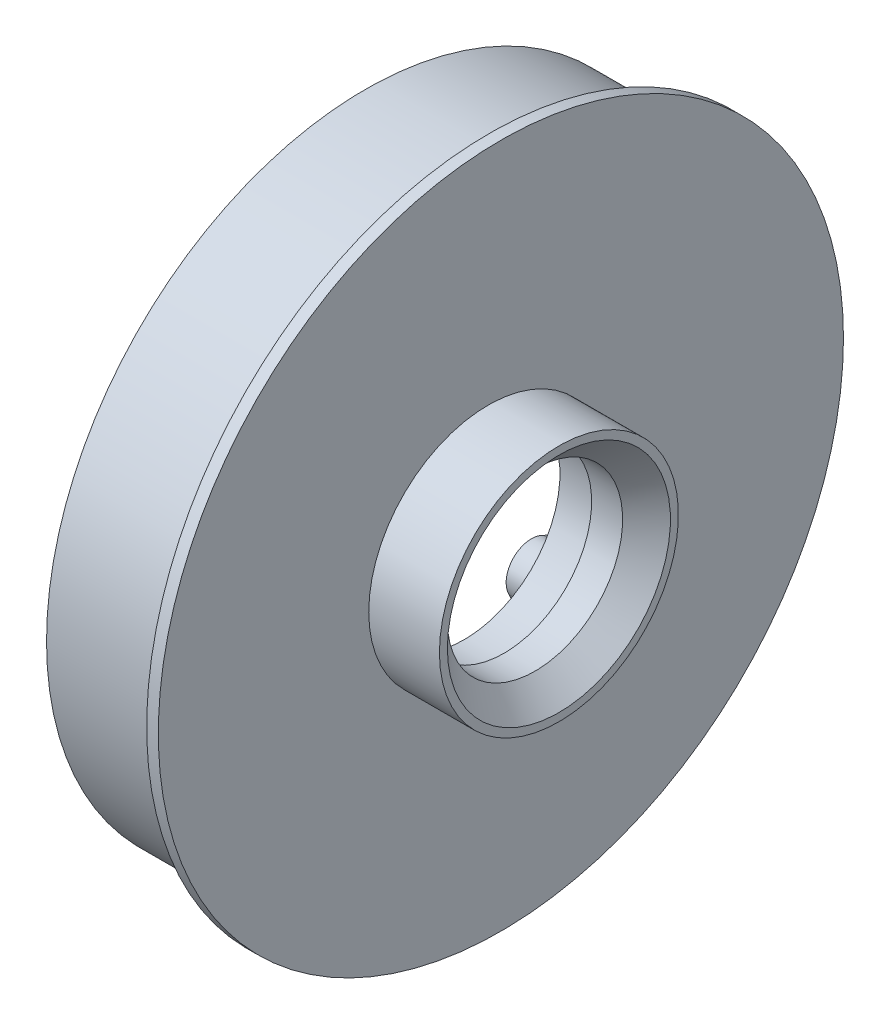
SolidWorks part; units mm, degrees
ref_plane "Front Plane" through (0, 0, 0) normal (0, 0, 1) x (1, 0, 0)
ref_plane "Top Plane" through (0, 0, 0) normal (0, 1, 0) x (1, 0, 0)
ref_plane "Right Plane" through (0, 0, 0) normal (1, 0, 0) x (0, 0, -1)
sketch "Sketch2" plane through (0, 0, 0) normal (0, 0, 1) x (1, 0, 0)
  line L0 (0, 0) -> (58.591, 0) construction
  line L2 (0, 0) -> (18.4, 0)
  line L3 (0, 0) -> (0, 2.5)
  line L4 (0, 2.5) -> (18.4, 2.5)
  line L5 (18.4, 0) -> (18.4, 2.5)
  line L6 (6.0094, 2.5) -> (6.0094, 6)
  line L11 (6.0094, 6) -> (9.9794, 6)
  line L16 (12.9794, 6) -> (12.9794, 3)
  line L17 (12.9794, 3) -> (13.6398, 3)
  line L18 (13.6398, 3) -> (13.6398, 2.5)
  line L19 (13.6398, 2.5) -> (6.0094, 2.5)
  line L22 (13.6398, 2.5) -> (16.1198, 2.5)
  line L23 (13.6398, 2.5) -> (13.6398, 4)
  line L24 (13.6398, 4) -> (16.1198, 4)
  line L25 (16.1198, 2.5) -> (16.1198, 4)
  line L27 (6.0094, 6) -> (9.9794, 6)
  line L28 (6.0094, 6) -> (6.0094, 9)
  line L29 (6.0094, 9) -> (9.9794, 9)
  line L30 (9.9794, 6) -> (9.9794, 9)
  line L31 (6.0094, 9) -> (6.0094, 8.25)
  line L32 (6.0094, 8.25) -> (5.0094, 8.25)
  line L33 (8.6609, 22.001) -> (8.6609, 12.476) construction
  line L34 (5.0094, 12.476) -> (12.3124, 12.476)
  line L35 (9.9794, 9) -> (12.3124, 9)
  line L36 (5.0094, 7.9375) -> (1.8344, 7.9375)
  line L37 (5.0094, 8.25) -> (5.0094, 12.476)
  line L38 (5.0094, 7.9375) -> (5.0094, 13.9365)
  line L39 (5.0094, 13.9365) -> (1.8344, 13.9365)
  line L40 (1.8344, 7.9375) -> (1.8344, 13.9365)
  line L41 (5.0094, 22.001) -> (12.3124, 22.001)
  line L42 (5.0094, 22.001) -> (5.0094, 30.1625)
  line L43 (5.0094, 30.1625) -> (12.3124, 30.1625)
  line L44 (12.3124, 22.001) -> (12.3124, 30.1625)
  line L49 (16.6398, 22.001) -> (16.6398, 7.5)
  line L51 (23.0198, 7.5) -> (23.0198, 6.5)
  line L54 (16.1198, 4) -> (13.6398, 4)
  line L56 (18.0398, 7.5) -> (23.0198, 7.5)
  line L57 (13.3124, 22.001) -> (16.6398, 22.001)
  line L58 (16.1198, 3.5) -> (20.0198, 3.5)
  line L59 (29.9098, 14) -> (26.9098, 11)
  line L60 (4.0094, 31.75) -> (18.0398, 31.75)
  line L61 (18.0398, 7.5) -> (23.0198, 7.5)
  line L62 (18.0398, 7.5) -> (18.0398, 12)
  line L63 (18.0398, 12) -> (23.0198, 12)
  line L64 (23.0198, 7.5) -> (23.0198, 12)
  line L65 (18.0398, 31.75) -> (18.0398, 12)
  line L66 (23.0198, 11) -> (26.9098, 11)
  line L67 (34.8098, 23) -> (31.3098, 19.5)
  line L68 (35.8098, 31) -> (38.7998, 33.99)
  line L69 (29.9098, 14) -> (29.9098, 15)
  line L70 (29.9098, 15) -> (22.9398, 15)
  line L71 (22.9398, 15) -> (21.0398, 15)
  line L72 (18.0398, 7.5) -> (16.6398, 7.5)
  line L73 (21.0398, 15) -> (21.0398, 43)
  line L74 (19.5798, 40) -> (9.6198, 40)
  line L75 (9.6198, 40) -> (4.0094, 40)
  line L76 (21.0398, 43) -> (19.5798, 43)
  line L77 (22.9398, 15) -> (29.9098, 15)
  line L78 (22.9398, 15) -> (22.9398, 21)
  line L79 (22.9398, 21) -> (29.9098, 21)
  line L80 (29.9098, 15) -> (29.9098, 21)
  line L81 (9.6198, 40) -> (19.5798, 40)
  line L82 (9.6198, 40) -> (9.6198, 50)
  line L83 (9.6198, 50) -> (19.5798, 50)
  line L84 (19.5798, 40) -> (19.5798, 50)
  line L85 (4.0094, 40) -> (4.0094, 31.75)
  line L86 (12.9794, 3) -> (12.9794, 2.5)
  line L87 (31.3098, 19.5) -> (29.9098, 19.5)
  line L88 (21.4694, 63.5) -> (21.4694, 51.308)
  line L89 (21.4694, 63.5) -> (25.9398, 63.5)
  line L90 (25.9398, 63.5) -> (25.9398, 25)
  line L91 (27.8398, 25) -> (25.9398, 25)
  line L92 (9.6198, 48) -> (8.1598, 48)
  line L93 (8.1598, 48) -> (8.1598, 53.476)
  line L94 (8.1598, 53.476) -> (19.5798, 53.476)
  line L95 (19.5798, 53.476) -> (19.5798, 50)
  line L96 (13.8698, 63.001) -> (13.8698, 53.476) construction
  line L97 (8.1598, 63.001) -> (19.5798, 63.001)
  line L98 (8.1598, 63.001) -> (8.1598, 68.2625)
  line L99 (8.1598, 68.2625) -> (19.5798, 68.2625)
  line L100 (19.5798, 63.001) -> (19.5798, 68.2625)
  line L101 (12.9794, 6) -> (11.9794, 6)
  line L102 (8.1598, 44.825) -> (4.9848, 44.825)
  line L103 (8.1598, 44.825) -> (8.1598, 54.9365)
  line L104 (8.1598, 54.9365) -> (4.9848, 54.9365)
  line L106 (9.9794, 6) -> (10.8794, 6)
  line L107 (27.8398, 25) -> (34.8098, 25)
  line L108 (34.8098, 25) -> (34.8098, 23)
  line L109 (0, 0) -> (-2, 0)
  line L110 (0, 0) -> (0, 11)
  line L111 (27.8398, 25) -> (34.8098, 25)
  line L112 (27.8398, 25) -> (27.8398, 32.5)
  line L113 (27.8398, 32.5) -> (34.8098, 32.5)
  line L114 (34.8098, 25) -> (34.8098, 32.5)
  line L115 (35.8098, 31) -> (34.8098, 31)
  line L116 (27.8398, 32.5) -> (27.8398, 64.5)
  line L117 (20.5373, 74.025) -> (6.2023, 74.025)
  line L118 (6.2023, 74.025) -> (6.2023, 76.2)
  line L119 (38.7998, 47.29) -> (30.8398, 55.25)
  line L120 (0, 11) -> (-2, 11)
  line L121 (38.7998, 43.815) -> (30.8623, 43.815)
  line L123 (-4.8152, 69.85) -> (1.5348, 76.2)
  line L124 (38.7998, 47.29) -> (38.7998, 33.99)
  line L125 (-2, 0) -> (-2, 11)
  line L126 (38.7998, 37.465) -> (30.8623, 37.465)
  line L127 (30.8623, 43.815) -> (30.8623, 37.465)
  line L128 (6.0094, 2.5) -> (6.0094, 0)
  line L129 (-0.0152, 63.5) -> (-0.0152, 30)
  line L132 (4.9848, 63.5) -> (-0.0152, 63.5)
  line L136 (-1.8152, 30) -> (-11.7752, 30)
  line L138 (-13.7752, 25.4) -> (-2, 25.4)
  line L139 (-2, 25.4) -> (-2, 11.5)
  line L140 (27.8398, 64.5) -> (20.5373, 64.5)
  line L141 (-1.8152, 30) -> (-11.7752, 30)
  line L142 (-1.8152, 30) -> (-1.8152, 39)
  line L143 (-1.8152, 39) -> (-11.7752, 39)
  line L144 (-11.7752, 30) -> (-11.7752, 39)
  line L145 (20.5373, 64.5) -> (20.5373, 74.025)
  line L146 (-12.7752, 37) -> (-12.7752, 47.29)
  line L147 (-12.7752, 37) -> (-11.7752, 37)
  line L148 (30.8398, 55.25) -> (30.8398, 76.2)
  line L149 (11.9794, 6) -> (11.9794, 5.45)
  line L154 (-2, 11.5) -> (0.5, 11.5)
  line L155 (4.9848, 60.6197) -> (24.0348, 60.6197)
  line L160 (4.9848, 60.6197) -> (4.9848, 55.8572)
  line L161 (4.9848, 55.8572) -> (24.0348, 55.8572)
  line L166 (24.0348, 60.6197) -> (24.0348, 55.8572)
  line L167 (4.9848, 60.6197) -> (24.0348, 55.8572) construction
  line L172 (4.9848, 55.8572) -> (24.0348, 60.6197) construction
  line L173 (24.0348, 62.2072) -> (25.9398, 62.2072)
  line L174 (11.9794, 5.45) -> (10.8794, 5.45)
  line L175 (10.8794, 6) -> (10.8794, 5.45)
  line L176 (24.0348, 62.2072) -> (24.0348, 54.2697)
  line L177 (24.0348, 54.2697) -> (25.9398, 54.2697)
  line L178 (25.9398, 62.2072) -> (25.9398, 54.2697)
  line L179 (24.0348, 62.2072) -> (25.9398, 54.2697) construction
  line L180 (24.0348, 54.2697) -> (25.9398, 62.2072) construction
  line L181 (3, 19.6197) -> (15.7, 19.6197)
  line L182 (3, 19.6197) -> (3, 14.8572)
  line L183 (3, 14.8572) -> (15.7, 14.8572)
  line L184 (15.7, 19.6197) -> (15.7, 14.8572)
  line L185 (3, 19.6197) -> (15.7, 14.8572) construction
  line L186 (3, 14.8572) -> (15.7, 19.6197) construction
  line L187 (15.7, 21.2072) -> (16.6398, 21.2072)
  line L188 (15.7, 21.2072) -> (15.7, 13.2697)
  line L189 (15.7, 13.2697) -> (16.6398, 13.2697)
  line L190 (16.6398, 21.2072) -> (16.6398, 13.2697)
  line L191 (15.7, 21.2072) -> (16.6398, 13.2697) construction
  line L192 (15.7, 13.2697) -> (16.6398, 21.2072) construction
  line L193 (0.5, 11.5) -> (0.5, 6.9375)
  line L194 (0.5, 6.9375) -> (1.8344, 6.9375)
  line L195 (23.0198, 6.5) -> (20.0198, 3.5)
  line L196 (4.9848, 63.5) -> (4.9848, 54.9365)
  line L197 (3, 43.825) -> (4.9848, 43.825)
  line L198 (1.8344, 6.9375) -> (1.8344, 7.9375)
  line L199 (6.0094, 0) -> (12.9794, 0)
  line L200 (12.9794, 0) -> (12.9794, 2.5)
  line L201 (18.0398, 31.75) -> (18.0398, 35.875)
  line L202 (18.0398, 35.875) -> (21.0398, 35.875)
  line L203 (30.8398, 76.2) -> (6.2023, 76.2)
  line L204 (2.7573, 69.85) -> (7.2023, 69.85) construction
  line L205 (7.2023, 67.4688) -> (26.2523, 67.4688)
  line L206 (7.2023, 74.025) -> (7.2023, 64.5)
  line L207 (7.2023, 64.5) -> (-1.8152, 64.5)
  line L208 (-1.8152, 64.5) -> (-1.8152, 39)
  line L209 (-12.7752, 47.29) -> (-4.8152, 55.25)
  line L210 (-4.8152, 55.25) -> (-4.8152, 69.85)
  line L211 (7.2023, 67.4688) -> (7.2023, 72.2312)
  line L212 (7.2023, 72.2312) -> (26.2523, 72.2313)
  line L213 (26.2523, 67.4688) -> (26.2523, 72.2313)
  line L214 (26.2523, 73.8187) -> (30.8398, 73.8187)
  line L215 (26.2523, 73.8187) -> (26.2523, 65.8813)
  line L216 (26.2523, 65.8813) -> (30.8398, 65.8813)
  line L217 (30.8398, 73.8187) -> (30.8398, 65.8813)
  line L218 (2.7573, 72.2313) -> (24.9823, 72.2313)
  line L219 (2.7573, 72.2313) -> (2.7573, 67.4687)
  line L220 (2.7573, 67.4687) -> (24.9823, 67.4687)
  line L221 (24.9823, 72.2313) -> (24.9823, 67.4687)
  line L222 (24.9823, 69.85) -> (20.5373, 69.85) construction
  line L223 (21.4694, 51.308) -> (22.9398, 51.308)
  line L224 (22.9398, 51.308) -> (22.9398, 21)
  line L225 (13.6398, 4) -> (13.6398, 12.2697)
  line L226 (13.6398, 12.2697) -> (13.3124, 12.2697)
  line L227 (13.3124, 12.2697) -> (13.3124, 22.001)
  line L228 (12.3124, 9) -> (12.3124, 12.476)
  line L229 (-1.8152, 30) -> (-0.0152, 30)
  line L230 (8.1598, 65.6317) -> (2.7573, 65.6317) construction
  line L231 (19.5798, 65.6317) -> (24.9823, 65.6317) construction
  line L232 (1.5348, 76.2) -> (6.2023, 76.2)
  line L233 (-11.7752, 30) -> (-13.7752, 30)
  line L234 (-13.7752, 30) -> (-13.7752, 25.4)
  line L235 (3, 13.9365) -> (3, 43.825)
  line L236 (4.9848, 54.9365) -> (4.9848, 44.825)
  line L237 (4.9848, 43.825) -> (4.9848, 44.825)
  circle A0 centre (26.8898, 25.95) radius 0.95
  circle A1 centre (21.9898, 15.95) radius 0.95
  circle A2 centre (17.3398, 8.2) radius 0.7
  circle A3 centre (10.4294, 6.45) radius 0.45
  circle A4 centre (-0.9152, 30.9) radius 0.9
  point P7 (24.9873, 58.2385)
  point P131 (16.1699, 17.2385)
  point P135 (14.5098, 58.2385)
  point P146 (9.35, 17.2385)
sketch "Sketch3" plane through (0, 0, 0) normal (1, 0, 0) x (0, 0, -1)
  line L0 (0, 0) -> (0, 69.85) construction
  line L1 (0, 0) -> (13.6271, 68.5079) construction
  line L2 (0, 0) -> (0, 58.2385) construction
  line L3 (0, 0) -> (50.436, 29.1192) construction
  line L4 (0, 0) -> (0, 31.75) construction
  line L5 (0, 0) -> (12.1502, 29.3332) construction
  line L6 (0, 0) -> (0, 17.2385) construction
  line L7 (0, 0) -> (14.929, 8.6192) construction
  line L8 (0, 0) -> (0, 58.2385) construction
  line L9 (0, 0) -> (50.436, 29.1192) construction
  line L10 (0, 0) -> (5.9583, 29.9542) construction
  line L11 (0, 0) -> (16.9677, 25.394) construction
  circle A0 centre (0, 0) radius 69.85 construction
  circle A1 centre (0, 0) radius 58.2385 construction
  circle A2 centre (0, 0) radius 31.75 construction
  circle A3 centre (0, 0) radius 17.2385 construction
  circle A4 centre (0, 69.85) radius 3.175
  circle A5 centre (0, 58.2385) radius 4.7625
  circle A6 centre (0, 31.75) radius 3.175
  circle A7 centre (0, 17.2385) radius 4.7625
  circle A8 centre (13.6271, 68.5079) radius 3.175
  circle A9 centre (26.7304, 64.533) radius 3.175
  circle A10 centre (38.8066, 58.0782) radius 3.175
  circle A11 centre (49.3914, 49.3914) radius 3.175
  circle A12 centre (58.0782, 38.8066) radius 3.175
  circle A13 centre (64.533, 26.7304) radius 3.175
  circle A14 centre (68.5079, 13.6271) radius 3.175
  circle A15 centre (69.85, 0) radius 3.175
  circle A16 centre (68.5079, -13.6271) radius 3.175
  circle A17 centre (64.533, -26.7304) radius 3.175
  circle A18 centre (58.0782, -38.8066) radius 3.175
  circle A19 centre (49.3914, -49.3914) radius 3.175
  circle A20 centre (38.8066, -58.0782) radius 3.175
  circle A21 centre (26.7304, -64.533) radius 3.175
  circle A22 centre (13.6271, -68.5079) radius 3.175
  circle A23 centre (0, -69.85) radius 3.175
  circle A24 centre (-13.6271, -68.5079) radius 3.175
  circle A25 centre (-26.7304, -64.533) radius 3.175
  circle A26 centre (-38.8066, -58.0782) radius 3.175
  circle A27 centre (-49.3914, -49.3914) radius 3.175
  circle A28 centre (-58.0782, -38.8066) radius 3.175
  circle A29 centre (-64.533, -26.7304) radius 3.175
  circle A30 centre (-68.5079, -13.6271) radius 3.175
  circle A31 centre (-69.85, 0) radius 3.175
  circle A32 centre (-68.5079, 13.6271) radius 3.175
  circle A33 centre (-64.533, 26.7304) radius 3.175
  circle A34 centre (-58.0782, 38.8066) radius 3.175
  circle A35 centre (-49.3914, 49.3914) radius 3.175
  circle A36 centre (-38.8066, 58.0782) radius 3.175
  circle A37 centre (-26.7304, 64.533) radius 3.175
  circle A38 centre (-13.6271, 68.5079) radius 3.175
  circle A47 centre (50.436, 29.1192) radius 4.7625
  circle A48 centre (50.436, -29.1192) radius 4.7625
  circle A49 centre (0, -58.2385) radius 4.7625
  circle A50 centre (-50.436, -29.1192) radius 4.7625
  circle A51 centre (-50.436, 29.1192) radius 4.7625
  circle A58 centre (12.1502, 29.3332) radius 3.175
  circle A59 centre (22.4506, 22.4506) radius 3.175
  circle A60 centre (29.3332, 12.1502) radius 3.175
  circle A61 centre (31.75, 0) radius 3.175
  circle A62 centre (29.3332, -12.1502) radius 3.175
  circle A63 centre (22.4506, -22.4506) radius 3.175
  circle A64 centre (12.1502, -29.3332) radius 3.175
  circle A65 centre (0, -31.75) radius 3.175
  circle A66 centre (-12.1502, -29.3332) radius 3.175
  circle A67 centre (-22.4506, -22.4506) radius 3.175
  circle A68 centre (-29.3332, -12.1502) radius 3.175
  circle A69 centre (-31.75, 0) radius 3.175
  circle A70 centre (-29.3332, 12.1502) radius 3.175
  circle A71 centre (-22.4506, 22.4506) radius 3.175
  circle A72 centre (14.929, 8.6192) radius 4.7625
  circle A73 centre (14.929, -8.6192) radius 4.7625
  circle A74 centre (0, -17.2385) radius 4.7625
  circle A75 centre (-14.929, -8.6192) radius 4.7625
  circle A76 centre (-14.929, 8.6192) radius 4.7625
  circle A77 centre (0, 0) radius 50
  circle A78 centre (0, 0) radius 9
  circle A79 centre (-12.1502, 29.3332) radius 3.175
  circle A80 centre (0, 0) radius 76.2
  circle A81 centre (0, 0) radius 74.025
  circle A82 centre (0, 69.85) radius 3.9687
  circle A83 centre (49.3914, 49.3914) radius 3.9687
  circle A84 centre (69.85, 0) radius 3.9688
  circle A85 centre (49.3914, -49.3914) radius 3.9687
  circle A86 centre (0, -69.85) radius 3.9687
  circle A87 centre (-49.3914, -49.3914) radius 3.9687
  circle A88 centre (-69.85, 0) radius 3.9688
  circle A89 centre (-49.3914, 49.3914) radius 3.9687
  circle A90 centre (0, 69.85) radius 2.3812
  circle A91 centre (13.6271, 68.5079) radius 2.3812
  circle A92 centre (26.7304, 64.533) radius 2.3813
  circle A93 centre (38.8066, 58.0782) radius 2.3812
  circle A94 centre (49.3914, 49.3914) radius 2.3812
  circle A95 centre (58.0782, 38.8066) radius 2.3812
  circle A96 centre (64.533, 26.7304) radius 2.3813
  circle A97 centre (68.5079, 13.6271) radius 2.3813
  circle A98 centre (69.85, 0) radius 2.3813
  circle A99 centre (68.5079, -13.6271) radius 2.3813
  circle A100 centre (64.533, -26.7304) radius 2.3813
  circle A101 centre (58.0782, -38.8066) radius 2.3812
  circle A102 centre (49.3914, -49.3914) radius 2.3812
  circle A103 centre (38.8066, -58.0782) radius 2.3812
  circle A104 centre (26.7304, -64.533) radius 2.3813
  circle A105 centre (13.6271, -68.5079) radius 2.3812
  circle A106 centre (0, -69.85) radius 2.3812
  circle A107 centre (-13.6271, -68.5079) radius 2.3812
  circle A108 centre (-26.7304, -64.533) radius 2.3813
  circle A109 centre (-38.8066, -58.0782) radius 2.3812
  circle A110 centre (-49.3914, -49.3914) radius 2.3812
  circle A111 centre (-58.0782, -38.8066) radius 2.3812
  circle A112 centre (-64.533, -26.7304) radius 2.3812
  arc A113 (3.0399, 30.8338) -> (8.9911, 29.65) centre (5.9583, 29.9542) cw
  arc A114 (14.6081, 27.3234) -> (19.6532, 23.9523) centre (16.9677, 25.394) cw
  arc A115 (23.9523, 19.6532) -> (27.3234, 14.6081) centre (25.394, 16.9677) cw
  arc A116 (29.65, 8.9911) -> (30.8338, 3.0399) centre (29.9542, 5.9583) cw
  arc A117 (30.8338, -3.0399) -> (29.65, -8.9911) centre (29.9542, -5.9583) cw
  arc A118 (27.3234, -14.6081) -> (23.9523, -19.6532) centre (25.394, -16.9677) cw
  arc A119 (19.6532, -23.9523) -> (14.6081, -27.3234) centre (16.9677, -25.394) cw
  arc A120 (8.9911, -29.65) -> (3.0399, -30.8338) centre (5.9583, -29.9542) cw
  arc A121 (-3.0399, -30.8338) -> (-8.9911, -29.65) centre (-5.9583, -29.9542) cw
  arc A122 (-14.6081, -27.3234) -> (-19.6532, -23.9523) centre (-16.9677, -25.394) cw
  arc A123 (-23.9523, -19.6532) -> (-27.3234, -14.6081) centre (-25.394, -16.9677) cw
  arc A124 (-29.65, -8.9911) -> (-30.8338, -3.0399) centre (-29.9542, -5.9583) cw
  arc A125 (-30.8338, 3.0399) -> (-29.65, 8.9911) centre (-29.9542, 5.9583) cw
  arc A126 (-27.3234, 14.6081) -> (-23.9523, 19.6532) centre (-25.394, 16.9677) cw
  arc A127 (-19.6532, 23.9523) -> (-14.6081, 27.3234) centre (-16.9677, 25.394) cw
  arc A128 (-8.9911, 29.65) -> (-3.0399, 30.8338) centre (-5.9583, 29.9542) cw
  arc A129 (26.9875, 0) -> (26.9932, 0.1932) centre (30.2705, 0) cw
  arc A130 (65.0988, 0.2771) -> (65.0875, 0) centre (68.4964, 0) ccw
  circle A131 centre (1.5875, 0) radius 40
  circle A132 centre (1.5875, 0) radius 2.5
  circle A133 centre (1.5875, 0) radius 3
  circle A134 centre (1.5875, 0) radius 43
  circle A135 centre (-68.5079, -13.6271) radius 2.3813
  circle A136 centre (-69.85, 0) radius 2.3813
  circle A137 centre (-68.5079, 13.6271) radius 2.3813
  circle A138 centre (-64.533, 26.7304) radius 2.3812
  circle A139 centre (-58.0782, 38.8066) radius 2.3812
  circle A140 centre (-49.3914, 49.3914) radius 2.3812
  circle A141 centre (-38.8066, 58.0782) radius 2.3812
  circle A142 centre (-26.7304, 64.533) radius 2.3813
  circle A143 centre (-13.6271, 68.5079) radius 2.3812
  circle A144 centre (0, 58.2385) radius 2.3812
  circle A145 centre (0, 58.2385) radius 3.9688
  circle A146 centre (50.436, 29.1192) radius 3.9688
  circle A147 centre (50.436, 29.1192) radius 2.3813
  circle A148 centre (50.436, -29.1192) radius 3.9687
  circle A149 centre (50.436, -29.1192) radius 2.3812
  circle A150 centre (0, -58.2385) radius 3.9687
  circle A151 centre (0, -58.2385) radius 2.3812
  circle A152 centre (-50.436, -29.1192) radius 3.9687
  circle A153 centre (-50.436, -29.1192) radius 2.3812
  circle A154 centre (-50.436, 29.1192) radius 3.9687
  circle A155 centre (-50.436, 29.1192) radius 2.3812
  spline S1 degree 4 number of poles 499 (26.9875, 0) -> (26.9932, 0.1932)
  spline S3 degree 4 number of poles 617 (65.0875, 0) -> (65.0988, 0.2771)
  point P116 (0, 0)
  point P225 (0, 0)
sketch "Sketch5" plane through (0, 0, 0) normal (0, 0, 1) x (1, 0, 0)
  line L0 (23.0198, 7.5) -> (23.0198, 12) construction
  line L2 (22.9398, 15) -> (21.0398, 15) construction
  line L3 (29.9098, 14) -> (29.9098, 15) construction
  line L4 (29.9098, 15) -> (22.9398, 15) construction
  line L5 (29.9098, 14) -> (26.9098, 11) construction
  line L6 (23.0198, 11) -> (26.9098, 11) construction
  line L7 (18.0398, 12) -> (23.0198, 12) construction
  line L8 (18.0398, 31.75) -> (18.0398, 12) construction
  line L10 (18.0398, 35.875) -> (21.0398, 35.875) construction
  line L11 (18.0398, 31.75) -> (18.0398, 35.875) construction
  line L12 (23.0198, 11) -> (23.0198, 12)
  line L14 (22.9398, 15) -> (21.0398, 15)
  line L15 (29.9098, 14) -> (29.9098, 15)
  line L16 (29.9098, 15) -> (22.9398, 15)
  line L17 (29.9098, 14) -> (26.9098, 11)
  line L18 (23.0198, 11) -> (26.9098, 11)
  line L19 (18.0398, 12) -> (23.0198, 12)
  line L20 (18.0398, 31.75) -> (18.0398, 12)
  line L22 (18.0398, 35.875) -> (21.0398, 35.875)
  line L23 (18.0398, 31.75) -> (18.0398, 35.875)
  line L24 (21.0398, 15) -> (21.0398, 43) construction
  line L25 (21.0398, 15) -> (21.0398, 35.875)
revolve "Revolve1" add sketch "Sketch5" angle 360 about L0
sketch "Sketch6" plane through (0, 0, 0) normal (1, 0, 0) x (0, 0, -1)
  arc A0 (19.6532, 23.9523) -> (14.6081, 27.3234) centre (16.9677, 25.394) ccw construction
  circle A1 centre (12.1502, 29.3332) radius 3.175 construction
  arc A2 (8.9911, 29.65) -> (3.0399, 30.8338) centre (5.9583, 29.9542) ccw construction
  circle A3 centre (0, 31.75) radius 3.175 construction
  arc A4 (-3.0399, 30.8338) -> (-8.9911, 29.65) centre (-5.9583, 29.9542) ccw construction
  circle A5 centre (22.4506, 22.4506) radius 3.175 construction
  arc A6 (27.3234, 14.6081) -> (23.9523, 19.6532) centre (25.394, 16.9677) ccw construction
  circle A7 centre (29.3332, 12.1502) radius 3.175 construction
  arc A8 (30.8338, 3.0399) -> (29.65, 8.9911) centre (29.9542, 5.9583) ccw construction
  circle A9 centre (31.75, 0) radius 3.175 construction
  arc A10 (29.65, -8.9911) -> (30.8338, -3.0399) centre (29.9542, -5.9583) ccw construction
  circle A11 centre (29.3332, -12.1502) radius 3.175 construction
  arc A12 (23.9523, -19.6532) -> (27.3234, -14.6081) centre (25.394, -16.9677) ccw construction
  circle A13 centre (22.4506, -22.4506) radius 3.175 construction
  arc A14 (14.6081, -27.3234) -> (19.6532, -23.9523) centre (16.9677, -25.394) ccw construction
  circle A15 centre (12.1502, -29.3332) radius 3.175 construction
  arc A16 (3.0399, -30.8338) -> (8.9911, -29.65) centre (5.9583, -29.9542) ccw construction
  circle A17 centre (0, -31.75) radius 3.175 construction
  arc A18 (-8.9911, -29.65) -> (-3.0399, -30.8338) centre (-5.9583, -29.9542) ccw construction
  circle A19 centre (-12.1502, -29.3332) radius 3.175 construction
  arc A20 (-19.6532, -23.9523) -> (-14.6081, -27.3234) centre (-16.9677, -25.394) ccw construction
  circle A21 centre (-22.4506, -22.4506) radius 3.175 construction
  arc A22 (-27.3234, -14.6081) -> (-23.9523, -19.6532) centre (-25.394, -16.9677) ccw construction
  circle A23 centre (-29.3332, -12.1502) radius 3.175 construction
  arc A24 (-30.8338, -3.0399) -> (-29.65, -8.9911) centre (-29.9542, -5.9583) ccw construction
  circle A25 centre (-31.75, 0) radius 3.175 construction
  arc A26 (-29.65, 8.9911) -> (-30.8338, 3.0399) centre (-29.9542, 5.9583) ccw construction
  circle A27 centre (-29.3332, 12.1502) radius 3.175 construction
  arc A28 (-23.9523, 19.6532) -> (-27.3234, 14.6081) centre (-25.394, 16.9677) ccw construction
  circle A29 centre (-12.1502, 29.3332) radius 3.175 construction
  arc A30 (-14.6081, 27.3234) -> (-19.6532, 23.9523) centre (-16.9677, 25.394) ccw construction
  circle A31 centre (-22.4506, 22.4506) radius 3.175 construction
  circle A32 centre (1.5875, 0) radius 43 construction
  arc A33 (19.6532, 23.9523) -> (14.6081, 27.3234) centre (16.9677, 25.394) ccw
  arc A34 (8.9911, 29.65) -> (14.6081, 27.3234) centre (12.1502, 29.3332) ccw
  arc A35 (8.9911, 29.65) -> (3.0399, 30.8338) centre (5.9583, 29.9542) ccw
  arc A36 (-3.0399, 30.8338) -> (3.0399, 30.8338) centre (0, 31.75) ccw
  arc A37 (-3.0399, 30.8338) -> (-8.9911, 29.65) centre (-5.9583, 29.9542) ccw
  arc A38 (19.6532, 23.9523) -> (23.9523, 19.6532) centre (22.4506, 22.4506) ccw
  arc A39 (27.3234, 14.6081) -> (23.9523, 19.6532) centre (25.394, 16.9677) ccw
  arc A40 (27.3234, 14.6081) -> (29.65, 8.9911) centre (29.3332, 12.1502) ccw
  arc A41 (30.8338, 3.0399) -> (29.65, 8.9911) centre (29.9542, 5.9583) ccw
  arc A42 (30.8338, 3.0399) -> (30.8338, -3.0399) centre (31.75, 0) ccw
  arc A43 (29.65, -8.9911) -> (30.8338, -3.0399) centre (29.9542, -5.9583) ccw
  arc A44 (29.65, -8.9911) -> (27.3234, -14.6081) centre (29.3332, -12.1502) ccw
  arc A45 (23.9523, -19.6532) -> (27.3234, -14.6081) centre (25.394, -16.9677) ccw
  arc A46 (23.9523, -19.6532) -> (19.6532, -23.9523) centre (22.4506, -22.4506) ccw
  arc A47 (14.6081, -27.3234) -> (19.6532, -23.9523) centre (16.9677, -25.394) ccw
  arc A48 (14.6081, -27.3234) -> (8.9911, -29.65) centre (12.1502, -29.3332) ccw
  arc A49 (3.0399, -30.8338) -> (8.9911, -29.65) centre (5.9583, -29.9542) ccw
  arc A50 (3.0399, -30.8338) -> (-3.0399, -30.8338) centre (0, -31.75) ccw
  arc A51 (-8.9911, -29.65) -> (-3.0399, -30.8338) centre (-5.9583, -29.9542) ccw
  arc A52 (-8.9911, -29.65) -> (-14.6081, -27.3234) centre (-12.1502, -29.3332) ccw
  arc A53 (-19.6532, -23.9523) -> (-14.6081, -27.3234) centre (-16.9677, -25.394) ccw
  arc A54 (-19.6532, -23.9523) -> (-23.9523, -19.6532) centre (-22.4506, -22.4506) ccw
  arc A55 (-27.3234, -14.6081) -> (-23.9523, -19.6532) centre (-25.394, -16.9677) ccw
  arc A56 (-27.3234, -14.6081) -> (-29.65, -8.9911) centre (-29.3332, -12.1502) ccw
  arc A57 (-30.8338, -3.0399) -> (-29.65, -8.9911) centre (-29.9542, -5.9583) ccw
  arc A58 (-30.8338, -3.0399) -> (-30.8338, 3.0399) centre (-31.75, 0) ccw
  arc A59 (-29.65, 8.9911) -> (-30.8338, 3.0399) centre (-29.9542, 5.9583) ccw
  arc A60 (-29.65, 8.9911) -> (-27.3234, 14.6081) centre (-29.3332, 12.1502) ccw
  arc A61 (-23.9523, 19.6532) -> (-27.3234, 14.6081) centre (-25.394, 16.9677) ccw
  arc A62 (-14.6081, 27.3234) -> (-8.9911, 29.65) centre (-12.1502, 29.3332) ccw
  arc A63 (-14.6081, 27.3234) -> (-19.6532, 23.9523) centre (-16.9677, 25.394) ccw
  arc A64 (-23.9523, 19.6532) -> (-19.6532, 23.9523) centre (-22.4506, 22.4506) ccw
  circle A65 centre (1.5875, 0) radius 43
extrude "Boss-Extrude1" add sketch "Sketch6" along normal up to vertex (21.0398 mm away) from vertex contours A65 A61 A64 A63 A62 A37 A36 A35 A34 A33 A38 A39 A40 A41 A42 A43 A44 A45 A46 A47 A48 A49 A50 A51 A52 A53 A54 A55 A56 A57 A58 A59 A60 region at (0, 0, 40.1963) up to point (21.0398, 43, 0) starting at point (4.0094, 40, 0)
sketch "Sketch7" plane through (0, 0, 0) normal (1, 0, 0) x (0, 0, -1)
  circle A0 centre (1.5875, 0) radius 43 construction
  circle A1 centre (1.5875, 0) radius 40 construction
  circle A2 centre (1.5875, 0) radius 43
  circle A3 centre (1.5875, 0) radius 40
extrude "Cut-Extrude1" cut sketch "Sketch7" along normal up to vertex (19.5798 mm away) up to point (19.5798, 40, 0)
